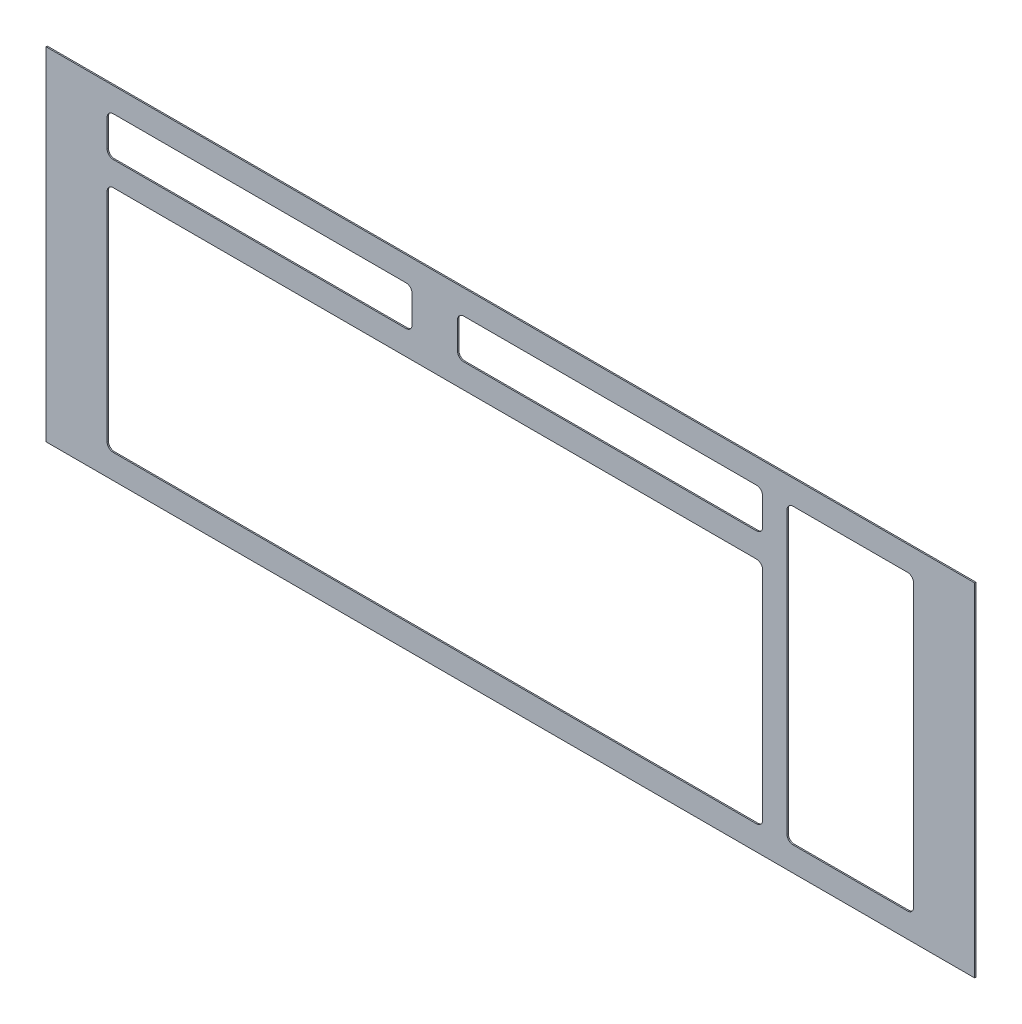
SolidWorks part; units mm, degrees
ref_plane "Front Plane" through (0, 0, 0) normal (0, 0, 1) x (1, 0, 0)
ref_plane "Top Plane" through (0, 0, 0) normal (0, 1, 0) x (1, 0, 0)
ref_plane "Right Plane" through (0, 0, 0) normal (1, 0, 0) x (0, 0, -1)
sketch "Sketch1" plane through (0, 0, 0) normal (0, 0, 1) x (1, 0, 0)
  line L1 (-51.3592, 186.2218) -> (431.2408, 186.2218)
  line L2 (-51.3592, 186.2218) -> (-51.3592, 8.4218)
  line L3 (-51.3592, 8.4218) -> (431.2408, 8.4218)
  line L4 (431.2408, 186.2218) -> (431.2408, 8.4218)
  dimension "D1" = 177.8
  dimension "D2" = 482.6
sheet metal parameters "Sheet-Metal1" thickness 0.6604 parameters "D1"=1.27
base flange "Base-Flange1" sketch "Sketch1" thickness 0.6604 reverse thickness direction no parameters "D1"=1.27
sketch "Sketch2" plane through (0, 0, 0) normal (0, 0, 1) x (1, 0, 0)
  line L0 (-51.3592, 186.2218) -> (-51.3592, 8.4218) construction
  line L1 (-19.6092, 173.5218) -> (138.8868, 173.5218)
  line L2 (-19.6092, 173.5218) -> (-19.6092, 152.9478)
  line L3 (-19.6092, 152.9478) -> (138.8868, 152.9478)
  line L4 (138.8868, 173.5218) -> (138.8868, 152.9478)
  line L5 (431.2408, 186.2218) -> (-51.3592, 186.2218) construction
  dimension "D1" = 158.496
  dimension "D2" = 20.574
  dimension "D3" = 31.75
  dimension "D4" = 12.7
extrude "Cut-Extrude1" cut sketch "Sketch2" against normal blind 0.6604 normal cut yes
pattern_linear "LPattern1" count 2 spacing 182.118 along (1, 0, 0) of "Cut-Extrude1"
sketch "Sketch3" plane through (0, 0, 0) normal (0, 0, 1) x (1, 0, 0)
  line L0 (-19.6092, 173.5218) -> (-19.6092, 152.9478) construction
  line L1 (-19.6092, 140.2478) -> (321.0048, 140.2478)
  line L2 (-19.6092, 140.2478) -> (-19.6092, 21.1218)
  line L3 (-19.6092, 21.1218) -> (321.0048, 21.1218)
  line L4 (321.0048, 140.2478) -> (321.0048, 21.1218)
  line L5 (321.0048, 152.9478) -> (321.0048, 173.5218) construction
  line L6 (-19.6092, 152.9478) -> (138.8868, 152.9478) construction
  line L7 (-51.3592, 8.4218) -> (431.2408, 8.4218) construction
  point P6 (321.0048, 163.2348)
  dimension "D1" = 0
  dimension "D2" = 0
  dimension "D3" = 12.7
  dimension "D4" = 12.7
extrude "Cut-Extrude2" cut sketch "Sketch3" against normal blind 0.6604 normal cut yes
sketch "Sketch4" plane through (0, 0, -0.6604) normal (0, 0, -1) x (-1, 0, 0)
  line L0 (19.6092, 21.1218) -> (-321.0048, 21.1218) construction
  line L1 (-399.4908, 173.5218) -> (-333.7048, 173.5218)
  line L2 (-399.4908, 173.5218) -> (-399.4908, 21.1218)
  line L3 (-399.4908, 21.1218) -> (-333.7048, 21.1218)
  line L4 (-333.7048, 173.5218) -> (-333.7048, 21.1218)
  line L5 (-321.0048, 173.5218) -> (-162.5088, 173.5218) construction
  line L6 (-321.0048, 21.1218) -> (-321.0048, 140.2478) construction
  line L7 (-431.2408, 8.4218) -> (-431.2408, 186.2218) construction
  dimension "D1" = 0
  dimension "D2" = 0
  dimension "D3" = 12.7
  dimension "D4" = 31.75
extrude "Cut-Extrude3" cut sketch "Sketch4" against normal blind 0.6604 normal cut yes
fillet "Fillet1" radius 3.175 16 edges at (-19.6092, 21.1218, -0.3302) (-19.6092, 140.2478, -0.3302) (138.8868, 152.9478, -0.3302) (138.8868, 173.5218, -0.3302) (-19.6092, 173.5218, -0.3302) (-19.6092, 152.9478, -0.3302) (162.5088, 152.9478, -0.3302) (162.5088, 173.5218, -0.3302) (321.0048, 152.9478, -0.3302) (321.0048, 173.5218, -0.3302) (321.0048, 140.2478, -0.3302) (321.0048, 21.1218, -0.3302) (399.4908, 21.1218, -0.3302) (333.7048, 21.1218, -0.3302) (333.7048, 173.5218, -0.3302) (399.4908, 173.5218, -0.3302)
flat pattern "Flat-Pattern1" [suppressed]
sketch "Bend-Lines1" plane through (0, 0, 0) normal (0, 1, 0) x (-1, 0, 0)
sketch3d "Bounding-Box1" [suppressed]
  line L0 (0, 0, 0) -> (-482.6, 0, 0) construction
  line L1 (0, 177.8, 0) -> (-482.6, 177.8, 0) construction
  line L2 (0, 0, 0) -> (0, 177.8, 0) construction
  line L3 (-482.6, 0, 0) -> (-482.6, 177.8, 0) construction
